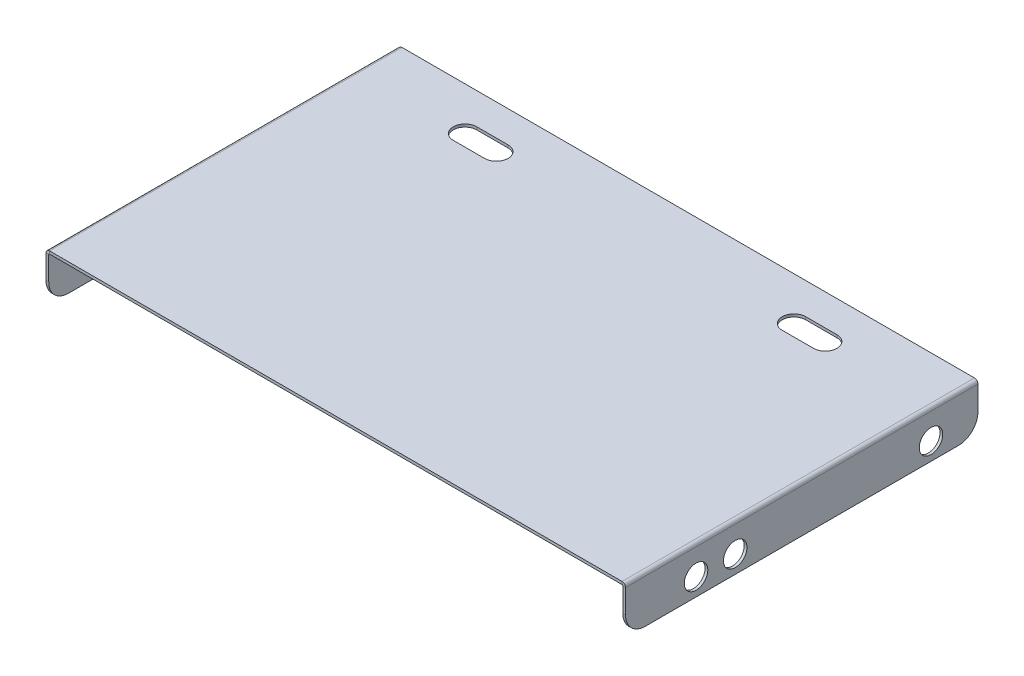
SolidWorks part; units mm, degrees
note: The reader was unsure of these and kept them because the rebuilt part matched: flange length of "边线-法兰1".
material "1023 碳钢板 (SS)"
ref_plane "前视基准面" through (0, 0, 0) normal (0, 0, 1) x (1, 0, 0)
ref_plane "上视基准面" through (0, 0, 0) normal (0, 1, 0) x (1, 0, 0)
ref_plane "右视基准面" through (0, 0, 0) normal (1, 0, 0) x (0, 0, -1)
sketch "草图1" plane through (0, 0, 0) normal (0, 1, 0) x (1, 0, 0)
  line L0 (-46, 34) -> (-38, 34) construction
  line L1 (-74, 45) -> (74, 45)
  line L2 (-74, 45) -> (-74, -45)
  line L3 (-74, -45) -> (74, -45)
  line L4 (74, 45) -> (74, -45)
  line L5 (-74, 45) -> (74, -45) construction
  line L6 (-74, -45) -> (74, 45) construction
  line L7 (-46, 37) -> (-38, 37)
  line L8 (-46, 31) -> (-38, 31)
  line L9 (38, 34) -> (46, 34) construction
  line L10 (38, 37) -> (46, 37)
  line L11 (38, 31) -> (46, 31)
  arc A0 (-46, 37) -> (-46, 31) centre (-46, 34) ccw
  arc A1 (-38, 31) -> (-38, 37) centre (-38, 34) ccw
  arc A2 (38, 37) -> (38, 31) centre (38, 34) ccw
  arc A3 (46, 31) -> (46, 37) centre (46, 34) ccw
  point P0 (0, 0)
  point P8 (-42, 34)
  point P13 (42, 34)
  point P20 (-42, 31)
  dimension "D7" = 28
  dimension "D8" = 28
  dimension "D1" = 148
  dimension "D2" = 90
  dimension "D3" = 8
  dimension "D4" = 8
  dimension "D5" = 6
  dimension "D6" = 6
  dimension "D9" = 8
base flange "基体-法兰1" sketch "草图1" thickness 0.7 reverse thickness direction no parameters "D1"=0.2
edge flange "边线-法兰1" sketch "草图12" flange profiles "草图12", "草图13" flange angle 90 flange length 12 flange position material inside bend radius 0.2 thickness 0.7 relief rectangular parameters "D6"=10, "D8"=1
sketch "草图12" plane through (74, -0.7, 0) normal (1, 0, 0) x (0, 0, 1)
  line L2 (-45, 0) -> (-45, 11.3)
  line L3 (-45, 11.3) -> (45, 11.3)
  line L4 (45, 11.3) -> (45, 0)
  line L7 (45, 0) -> (-45, 0) construction
  line L8 (45, 0) -> (-45, 0)
  line L9 (45, -0.7) -> (-45, -0.7) construction
  circle A0 centre (-33, 6.8) radius 3
  circle A1 centre (17, 6.8) radius 3
  circle A2 centre (27, 6.8) radius 3
  point P12 (-47.4901, 6.2765)
  point P13 (0, 0)
  point P14 (0, 0)
  dimension "D1" = 6
  dimension "D2" = 4.5
  dimension "D3" = 12
  dimension "D4" = 50
  dimension "D5" = 7.5
  dimension "D6" = 10
sketch "草图13" plane through (-74, -0.7, 0) normal (-1, 0, 0) x (0, 0, -1)
  line L2 (-45, 0) -> (-45, 11.3)
  line L3 (-45, 11.3) -> (45, 11.3)
  line L4 (45, 11.3) -> (45, 0)
  line L7 (45, 0) -> (-45, 0) construction
  line L8 (45, 0) -> (-45, 0)
bend "边线折弯1" bend radius 0.2 bend angle 90 parameters "D5"=1
bend "边线折弯2" bend radius 0.2 bend angle 90 parameters "D5"=2
fillet "圆角2" radius 5 4 edges at (73.65, -12, -45) (73.65, -12, 45) (-73.65, -12, 45) (-73.65, -12, -45)
sketch "草图15" plane through (-74, 0, 0) normal (-1, 0, 0) x (0, 0, 1)
  circle A0 centre (-33, -7.5) radius 3
  circle A1 centre (17, -7.5) radius 3
  circle A2 centre (27, -7.5) radius 3
  point P7 (0, 0)
  dimension "D1" = 6
  dimension "D2" = 10
  dimension "D3" = 50
extrude "切除-拉伸1" cut sketch "草图15" against normal blind 10
sketch "折弯-线1" plane through (0, 0, 0) normal (0, 1, 0) x (1, 0, 0)
sketch "边界框1" plane through (0, 0, 0) normal (0, 1, 0) x (1, 0, 0)
sheet metal parameters "钣金6" thickness 0.7 parameters "D1"=0.2
flat pattern "平板型式6" [suppressed]
sketch "折弯-线2" plane through (0, 0, 0) normal (0, 1, 0) x (1, 0, 0)
sketch "边界框2" [suppressed] plane through (0, 0, 0) normal (0, 1, 0) x (1, 0, 0)
sheet metal parameters "钣金7" thickness 0.7 parameters "D1"=0.2
flat pattern "平板型式6" [suppressed]
sketch "折弯-线2" plane through (0, 0, 0) normal (0, 1, 0) x (1, 0, 0)
sketch "边界框2" [suppressed] plane through (0, 0, 0) normal (0, 1, 0) x (1, 0, 0)
bend of the flat pattern "展平-<边线折弯1>1"
bend of the flat pattern "展平-<边线折弯2>1"
sheet metal parameters "钣金9" thickness 0.7 parameters "D1"=0.2
flat pattern "平板型式6" [suppressed]
sketch "折弯-线2" plane through (0, 0, 0) normal (0, 1, 0) x (1, 0, 0)
sketch "边界框2" [suppressed] plane through (0, 0, 0) normal (0, 1, 0) x (1, 0, 0)
bend of the flat pattern "展平-<边线折弯1>1"
bend of the flat pattern "展平-<边线折弯2>1"
